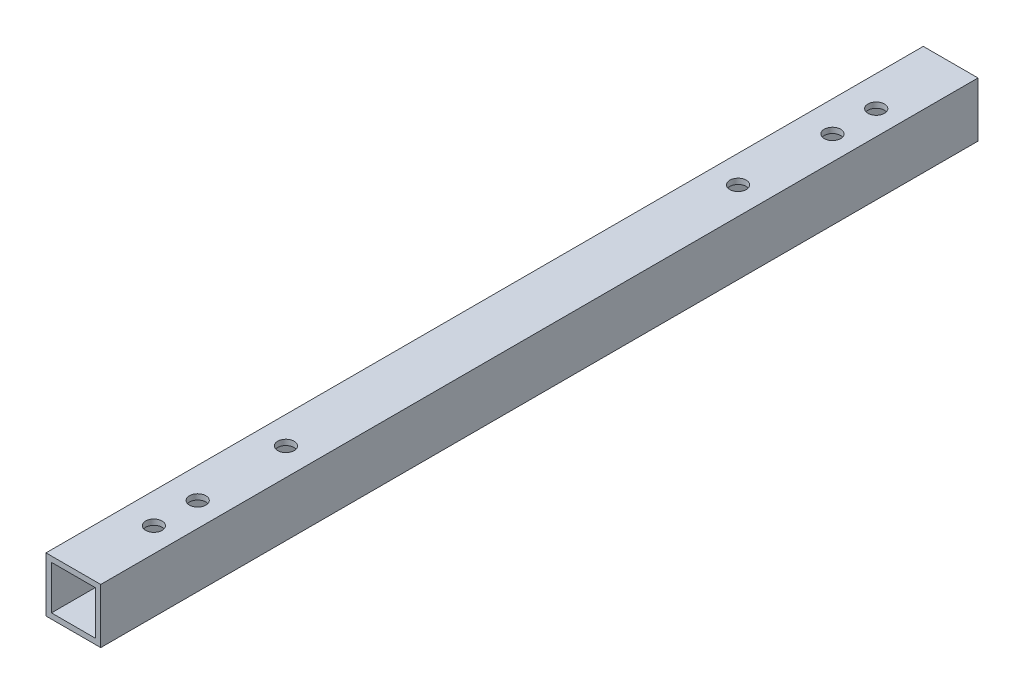
SolidWorks part; units mm, degrees
material "Thornel Mat VMA"
ref_plane "前视基准面" through (0, 0, 0) normal (0, 0, 1) x (1, 0, 0)
ref_plane "上视基准面" through (0, 0, 0) normal (0, 1, 0) x (1, 0, 0)
ref_plane "右视基准面" through (0, 0, 0) normal (1, 0, 0) x (0, 0, -1)
sketch "草图1" plane through (0, 0, 0) normal (0, 0, 1) x (1, 0, 0)
  line L1 (5, 5) -> (-5, 5)
  line L2 (5, 5) -> (5, -5)
  line L3 (5, -5) -> (-5, -5)
  line L4 (-5, 5) -> (-5, -5)
  line L5 (5, 5) -> (-5, -5) construction
  line L6 (5, -5) -> (-5, 5) construction
  line L7 (4, 4) -> (-4, 4)
  line L8 (4, 4) -> (4, -4)
  line L9 (4, -4) -> (-4, -4)
  line L10 (-4, 4) -> (-4, -4)
  line L11 (4, 4) -> (-4, -4) construction
  line L12 (4, -4) -> (-4, 4) construction
  point P0 (0, 0)
  point P6 (0, 0)
  dimension "D1" = 10
  dimension "D2" = 1
extrude "凸台-拉伸1" add sketch "草图1" along normal mid plane 160.31
hole_wizard "孔1" positions "草图2" profile "草图3" legacy end condition through all
sketch "草图2" plane through (0, -5, 0) normal (0, -1, 0) x (-1, 0, 0)
  point P0 (0.0035, -41.3127)
  point P3 (0.0035, 41.3127)
sketch "草图3" plane through (-0.0035, -5, 41.3127) normal (1, 0, 0) x (0, 0, -1)
  line L0 (0, 0) -> (0, 10)
  line L1 (0, 10) -> (1.5, 10)
  line L2 (1.5, 10) -> (1.5, 0)
  line L3 (1.5, 0) -> (0, 0)
  line L4 (0, 110) -> (0, -10) construction
  dimension "直径" = 3
  dimension "深度" = 10
hole_wizard "孔2" positions "草图8" profile "草图9" legacy end condition through all
sketch "草图8" plane through (0, 5, 0) normal (0, 1, 0) x (1, 0, 0)
  point P0 (0.5564, 66)
  point P2 (0.5564, 58)
  point P4 (0.5636, -58)
  point P6 (0.5564, -66)
sketch "草图9" plane through (0.5564, 5, -66) normal (1, 0, 0) x (0, 0, 1)
  line L0 (0, 0) -> (0, 10)
  line L1 (0, 10) -> (1.5, 10)
  line L2 (1.5, 10) -> (1.5, 0)
  line L3 (1.5, 0) -> (0, 0)
  line L4 (0, 110) -> (0, -10) construction
  dimension "直径" = 3
  dimension "深度" = 10
